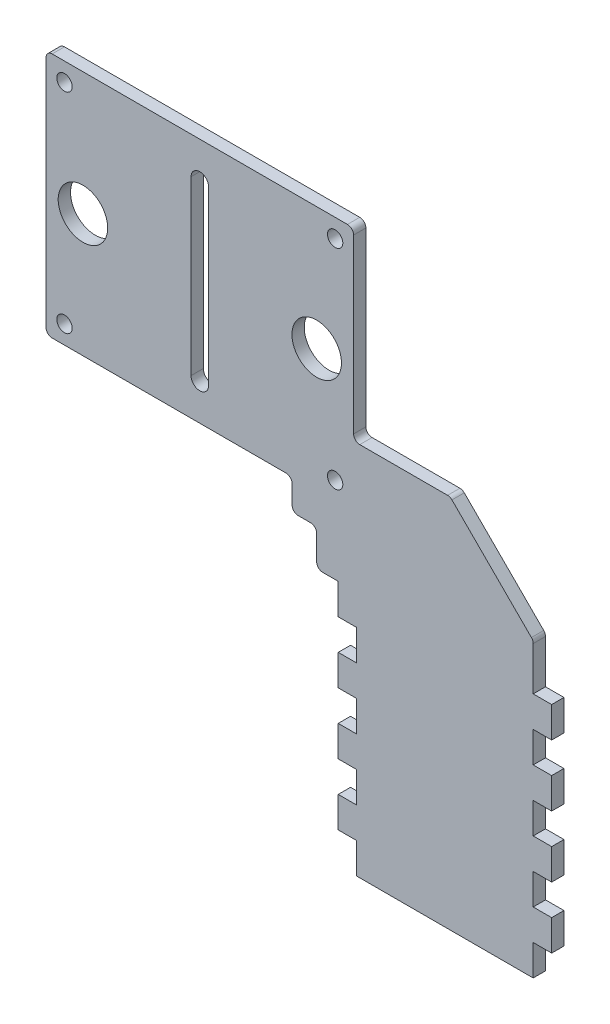
SolidWorks part; units mm, degrees
ref_plane "Front Plane" through (0, 0, 0) normal (0, 0, 1) x (1, 0, 0)
ref_plane "Top Plane" through (0, 0, 0) normal (0, 1, 0) x (1, 0, 0)
ref_plane "Right Plane" through (0, 0, 0) normal (1, 0, 0) x (0, 0, -1)
sketch "Sketch1" plane through (0, 0, 0) normal (0, 0, 1) x (1, 0, 0)
  line L1 (0, 0) -> (50, 0)
  line L2 (0, 0) -> (0, 40)
  line L3 (0, 40) -> (50, 40)
  line L4 (50, 0) -> (50, 40)
  line L5 (50, 0) -> (79.2, 0)
  line L6 (50, 0) -> (50, -51)
  line L7 (50, -51) -> (79.2, -51)
  line L8 (79.2, 0) -> (79.2, -51)
  line L9 (50, 0) -> (79.2, 0)
  line L12 (79.2, 0) -> (79.2, -21)
  line L13 (79.2, 0) -> (50, 0)
  line L14 (79.2, 0) -> (79.2, 10)
  line L15 (79.2, 10) -> (50, 10)
  line L16 (50, 0) -> (50, 10)
  line L17 (40, 0) -> (50, 0)
  line L18 (40, 0) -> (40, -5)
  line L19 (40, -5) -> (50, -5)
  line L20 (50, 0) -> (50, -5)
  line L21 (50, -5) -> (44, -5)
  line L22 (50, -5) -> (50, -11)
  line L23 (50, -11) -> (44, -11)
  line L24 (44, -5) -> (44, -11)
  dimension "D1" = 50
  dimension "D2" = 40
  dimension "D3" = 29.2
  dimension "D4" = 51
  dimension "D5" = 0
  dimension "D6" = 10
  dimension "D7" = 0
  dimension "D8" = 0
  dimension "D9" = 0
  dimension "D10" = 10
  dimension "D11" = 5
  dimension "D12" = 0
  dimension "D13" = 0
  dimension "D14" = 6
  dimension "D15" = 6
extrude "plate_body" add sketch "Sketch1" along normal blind 2 contours L1 L4 L3 L2 | L8 L5 L1 L6 L7 | L14 L15 L4 L5 | L18 L19 L6 L1 | L19 L24 L23 L6 region at (25, 20, 0) region at (45, -2.5, 0) region at (64.6, 5, 0) region at (64.6, -25.5, 0) region at (47, -8, 0)
sketch "Sketch2" plane through (0, 0, 2) normal (0, 0, 1) x (1, 0, 0)
  line L2 (0, 0) -> (0, 40) construction
  line L3 (0, 40) -> (50, 40) construction
  circle A0 centre (6, 20) radius 4.0238
  circle A1 centre (44, 20) radius 4.0238
  dimension "D1" = 38
  dimension "D2" = 8.0476
  dimension "D3" = 8.0476
  dimension "D4" = 6
  dimension "D5" = 20
  dimension "D6" = 20
extrude "shaft_bearings" cut sketch "Sketch2" against normal through all
sketch "Sketch4" plane through (0, 0, 2) normal (0, 0, 1) x (1, 0, 0)
  line L0 (25, 34) -> (25, 6) construction
  line L1 (26.425, 34) -> (26.425, 6)
  line L2 (23.575, 34) -> (23.575, 6)
  line L3 (0, 0) -> (40, 0) construction
  line L5 (0, 0) -> (0, 40) construction
  arc A0 (26.425, 34) -> (23.575, 34) centre (25, 34) ccw
  arc A1 (23.575, 6) -> (26.425, 6) centre (25, 6) ccw
  point P2 (25, 20)
  dimension "D4" = 6
  dimension "D1" = 2.85
  dimension "D2" = 28
  dimension "D3" = 25
extrude "slot" cut sketch "Sketch4" against normal through all
sketch "Sketch5" plane through (0, 0, 2) normal (0, 0, 1) x (1, 0, 0)
  line L0 (0, 40) -> (50, 40) construction
  line L1 (0, 0) -> (0, 40) construction
  line L3 (50, 10) -> (50, 40) construction
  line L4 (0, 0) -> (40, 0) construction
  circle A0 centre (3, 37) radius 1.25
  circle A1 centre (47, 37) radius 1.25
  circle A2 centre (3, 3) radius 1.25
  circle A3 centre (47, 3) radius 1.25
  dimension "D1" = 2.5
  dimension "D2" = 2.5
  dimension "D3" = 2.5
  dimension "D4" = 2.5
  dimension "D5" = 3
  dimension "D6" = 3
  dimension "D7" = 3
  dimension "D8" = 3
  dimension "D9" = 3
  dimension "D10" = 3
  dimension "D11" = 3
  dimension "D12" = 3
extrude "bolt_holes" cut sketch "Sketch5" against normal through all
sketch "Sketch6" plane through (0, 0, 2) normal (0, 0, 1) x (1, 0, 0)
  line L0 (50, -51) -> (79.2, -51) construction
  line L1 (50, -11) -> (50.5, -11)
  line L2 (50, -11) -> (50, -51)
  line L3 (50, -51) -> (50.5, -51)
  line L4 (50.5, -11) -> (50.5, -51)
  line L5 (50, -11) -> (44, -11) construction
  dimension "D1" = 0.5
  dimension "D2" = 0
extrude "Cut-Extrude1" cut sketch "Sketch6" against normal through all
sketch "Sketch8" plane through (0, 0, 2) normal (0, 0, 1) x (1, 0, 0)
  line L0 (50.5, -36) -> (47.5, -36)
  line L1 (50.5, -46) -> (47.5, -46)
  line L2 (50.5, -46) -> (50.5, -41)
  line L3 (50.5, -41) -> (47.5, -41)
  line L4 (47.5, -46) -> (47.5, -41)
  line L5 (79.2, -46) -> (82.2, -46)
  line L6 (79.2, -46) -> (79.2, -41)
  line L7 (79.2, -41) -> (82.2, -41)
  line L8 (82.2, -46) -> (82.2, -41)
  line L9 (50.5, -36) -> (50.5, -31)
  line L10 (50.5, -31) -> (47.5, -31)
  line L11 (47.5, -36) -> (47.5, -31)
  line L12 (79.2, -36) -> (82.2, -36)
  line L13 (79.2, -36) -> (79.2, -31)
  line L14 (79.2, -31) -> (82.2, -31)
  line L15 (82.2, -36) -> (82.2, -31)
  line L16 (50.5, -51) -> (50.5, -11) construction
  line L17 (79.2, -51) -> (79.2, 10) construction
  line L18 (50.5, -16) -> (47.5, -16)
  line L19 (50.5, -26) -> (47.5, -26)
  line L20 (50.5, -26) -> (50.5, -21)
  line L21 (50.5, -21) -> (47.5, -21)
  line L22 (47.5, -26) -> (47.5, -21)
  line L23 (79.2, -26) -> (82.2, -26)
  line L24 (79.2, -26) -> (79.2, -21)
  line L25 (79.2, -21) -> (82.2, -21)
  line L26 (82.2, -26) -> (82.2, -21)
  line L27 (50.5, -16) -> (50.5, -11)
  line L28 (50.5, -11) -> (47.5, -11)
  line L29 (47.5, -16) -> (47.5, -11)
  line L30 (79.2, -16) -> (82.2, -16)
  line L31 (79.2, -16) -> (79.2, -11)
  line L32 (79.2, -11) -> (82.2, -11)
  line L33 (82.2, -16) -> (82.2, -11)
  line L34 (50.5, -51) -> (79.2, -51) construction
  point P38 (80.7, -31)
  point P41 (80.7, -41)
  dimension "D1" = 5
  dimension "D2" = 5
  dimension "D3" = 3
  dimension "D4" = 3
  dimension "D5" = 5
  dimension "D6" = 5
  dimension "D7" = 3
  dimension "D8" = 3
  dimension "D9" = 0
  dimension "D10" = 0
  dimension "D11" = 5
  dimension "D12" = 5
  dimension "D13" = 5
  dimension "D14" = 5
  dimension "D15" = 3
  dimension "D16" = 3
  dimension "D17" = 5
  dimension "D18" = 5
  dimension "D19" = 3
  dimension "D20" = 3
  dimension "D21" = 5
  dimension "D22" = 5
  dimension "D25" = 0
  dimension "D26" = 0
  dimension "D27" = 5
  dimension "D28" = 5
  dimension "D29" = 10
  dimension "D30" = 10
extrude "finger_joints" add sketch "Sketch8" along direction (0, 0, 1) on the side against the normal up to surface (2 mm away) up to face at (48.25, 37, 0)
sketch "Sketch9" plane through (0, 0, 2) normal (0, 0, 1) x (1, 0, 0)
  line L0 (50.5, -51) -> (79.2, -51) construction
  line L1 (57, -21) -> (67, -21)
  line L2 (57, -21) -> (57, -41)
  line L3 (57, -41) -> (67, -41)
  line L4 (67, -21) -> (67, -41)
  line L5 (50.5, -51) -> (50.5, -46) construction
  dimension "D1" = 10
  dimension "D2" = 20
  dimension "D3" = 10
  dimension "D4" = 6.5
extrude "Cut-Extrude2" [suppressed] cut sketch "Sketch9" against normal through all
sketch "Sketch10" plane through (0, 0, 2) normal (0, 0, 1) x (1, 0, 0)
  line L0 (0, 40) -> (50, 40) construction
  line L1 (9.3, 40) -> (24.3, 40)
  line L2 (9.3, 40) -> (9.3, 50)
  line L3 (9.3, 50) -> (24.3, 50)
  line L4 (24.3, 40) -> (24.3, 50)
  circle A0 centre (16.8, 45) radius 1.5
  arc A1 (26.425, 34) -> (23.575, 34) centre (25, 34) ccw construction
  point P11 (25, 35.425)
  dimension "D4" = 7.5
  dimension "D5" = 5
  dimension "D6" = 3
  dimension "D3" = 8.2
  dimension "D1" = 10
  dimension "D2" = 15
extrude "tail_rod_mount" [suppressed] add sketch "Sketch10" against normal up to surface (2 mm away) up to face at (59.5619, -22, 0)
sketch "Sketch12" plane through (0, 0, 2) normal (0, 0, 1) x (1, 0, 0)
  line L0 (65.7, 10) -> (79.2, -3.5)
  line L1 (79.2, 10) -> (65.7, 10)
  line L2 (79.2, 10) -> (79.2, -3.5)
  line L3 (79.2, -3.5) -> (65.7, -3.5)
  line L4 (65.7, 10) -> (65.7, -3.5)
  point P5 (79.2, 3.25)
  dimension "D1" = 13.5
  dimension "D2" = 13.5
extrude "Cut-Extrude3" cut sketch "Sketch12" against normal blind 10 contours L2 L1 L0 region at (74.7, 5.5, 2)
fillet "1mm_fillets" radius 1 10 edges at (44, -11, 1) (44, -5, 1) (40, -5, 1) (40, 0, 1) (50, 10, 1) (50, 40, 1) (0, 0, 1) (0, 40, 1) (79.2, -3.5, 1) (65.7, 10, 1)
